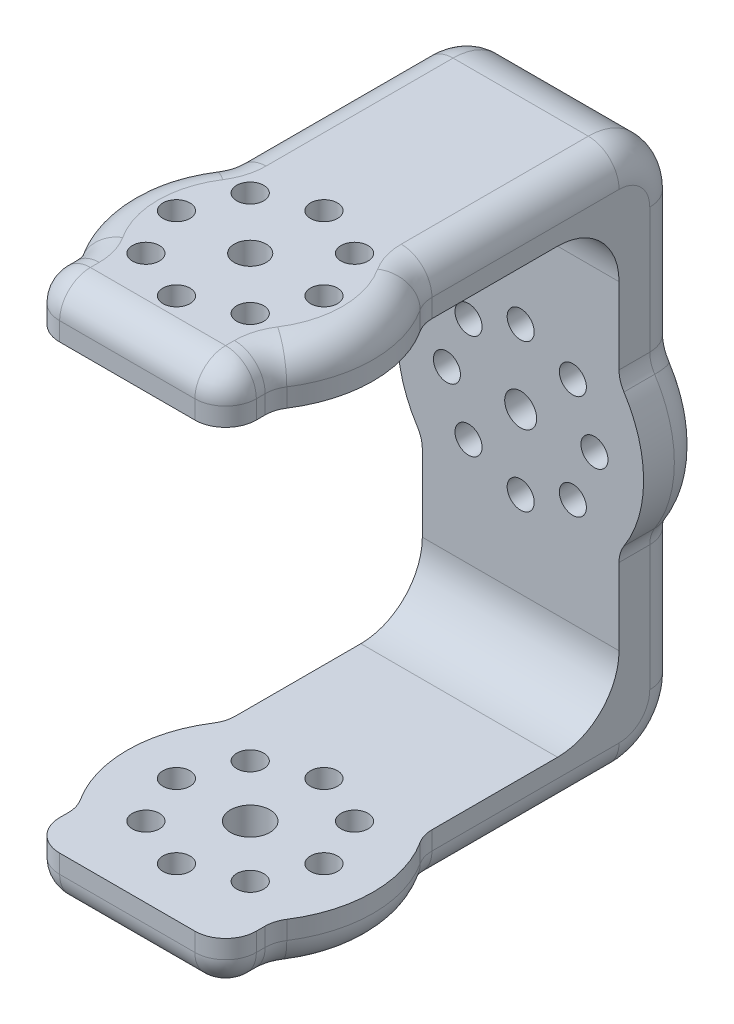
SolidWorks part; units mm, degrees
material "ABS"
ref_plane "正面" through (0, 0, 0) normal (0, 0, 1) x (1, 0, 0)
ref_plane "平面" through (0, 0, 0) normal (0, 1, 0) x (1, 0, 0)
ref_plane "右側面" through (0, 0, 0) normal (1, 0, 0) x (0, 0, -1)
sketch "ｽｹｯﾁ1" plane through (0, 0, 0) normal (0, 0, 1) x (1, 0, 0)
  line L0 (0, 0) -> (0, 36) construction
  line L1 (-8, 0) -> (8, 0)
  line L2 (-8, 0) -> (-8, 12)
  line L3 (-8, 36) -> (8, 36)
  line L4 (8, 0) -> (8, 12)
  line L5 (-8, 24) -> (-8, 36)
  line L6 (8, 24) -> (8, 36)
  circle A0 centre (0, 18) radius 6 construction
  circle A1 centre (0, 18) radius 1.3
  circle A2 centre (0, 24) radius 1.1
  circle A3 centre (4.2426, 22.2426) radius 1.1
  circle A4 centre (6, 18) radius 1.1
  circle A5 centre (4.2426, 13.7574) radius 1.1
  circle A6 centre (0, 12) radius 1.1
  circle A7 centre (-4.2426, 13.7574) radius 1.1
  circle A8 centre (-6, 18) radius 1.1
  circle A9 centre (-4.2426, 22.2426) radius 1.1
  arc A10 (-8, 24) -> (-8, 12) centre (0, 18) ccw
  arc A11 (8, 12) -> (8, 24) centre (0, 18) ccw
  point P29 (0, 18)
  dimension "D3" = 2.6
  dimension "D4" = 12
  dimension "D5" = 2.2
  dimension "D7" = 20
  dimension "D1" = 16
  dimension "D2" = 36
  dimension "D6" = 8
extrude "ﾎﾞｽ - 押し出し1" add sketch "ｽｹｯﾁ1" along normal blind 5
sketch "ｽｹｯﾁ2" plane through (0, 0, 0) normal (0, -1, 0) x (1, 0, 0)
  line L0 (8, 5) -> (8, 0) construction
  line L1 (-8, 0) -> (8, 0)
  line L2 (-8, 0) -> (-8, 21)
  line L3 (-8, 37) -> (8, 37)
  line L4 (8, 0) -> (8, 21)
  line L5 (0, 37) -> (0, 0) construction
  line L6 (-8, 33) -> (-8, 37)
  line L7 (8, 33) -> (8, 37)
  circle A0 centre (0, 27) radius 1.6
  circle A1 centre (0, 27) radius 6 construction
  circle A2 centre (6, 27) radius 1.1
  circle A3 centre (4.2426, 22.7574) radius 1.1
  circle A4 centre (0, 21) radius 1.1
  circle A5 centre (-4.2426, 22.7574) radius 1.1
  circle A6 centre (-6, 27) radius 1.1
  circle A7 centre (-4.2426, 31.2426) radius 1.1
  circle A8 centre (0, 33) radius 1.1
  circle A9 centre (4.2426, 31.2426) radius 1.1
  arc A10 (-8, 33) -> (-8, 21) centre (0, 27) ccw
  arc A11 (8, 21) -> (8, 33) centre (0, 27) ccw
  point P32 (0, 27)
  dimension "D2" = 12
  dimension "D3" = 3.2
  dimension "D5" = 2.2
  dimension "D7" = 10
  dimension "D1" = 37
  dimension "D4" = 10
  dimension "D6" = 8
extrude "ﾎﾞｽ - 押し出し2" add sketch "ｽｹｯﾁ2" along normal blind 4
sketch "ｽｹｯﾁ3" plane through (0, 36, 0) normal (0, 1, 0) x (1, 0, 0)
  line L0 (8, -5) -> (8, 0)
  line L1 (8, 0) -> (-8, 0)
  line L2 (-8, 0) -> (-8, -5)
  line L6 (8, -5) -> (-8, -5)
  line L7 (-8, -5) -> (-8, -21)
  line L8 (-8, -33) -> (-8, -37)
  line L9 (-8, -37) -> (8, -37)
  line L10 (8, -37) -> (8, -33)
  line L11 (8, -21) -> (8, -5)
  line L13 (-8, -5) -> (-8, -21)
  line L14 (-8, -33) -> (-8, -37)
  line L15 (-8, -37) -> (8, -37)
  line L16 (8, -37) -> (8, -33)
  line L17 (8, -21) -> (8, -5)
  circle A0 centre (4.2426, -22.7574) radius 1.1 construction
  circle A1 centre (0, -21) radius 1.1 construction
  arc A2 (-8, -21) -> (-8, -33) centre (0, -27) ccw
  arc A3 (8, -33) -> (8, -21) centre (0, -27) ccw
  arc A4 (-8, -21) -> (-8, -33) centre (0, -27) ccw
  arc A5 (8, -33) -> (8, -21) centre (0, -27) ccw
  circle A6 centre (-4.2426, -22.7574) radius 1.1 construction
  circle A7 centre (-6, -27) radius 1.1 construction
  circle A8 centre (-4.2426, -31.2426) radius 1.1 construction
  circle A9 centre (0, -33) radius 1.1 construction
  circle A10 centre (4.2426, -31.2426) radius 1.1 construction
  circle A11 centre (6, -27) radius 1.1 construction
  circle A12 centre (4.2426, -22.7574) radius 1.1
  circle A13 centre (0, -21) radius 1.1
  circle A14 centre (-4.2426, -22.7574) radius 1.1
  circle A15 centre (-6, -27) radius 1.1
  circle A16 centre (-4.2426, -31.2426) radius 1.1
  circle A17 centre (0, -33) radius 1.1
  circle A18 centre (4.2426, -31.2426) radius 1.1
  circle A19 centre (6, -27) radius 1.1
  circle A20 centre (0, -27) radius 1.3
  dimension "D2" = 2.6
  dimension "D1" = 0
extrude "ﾎﾞｽ - 押し出し3" add sketch "ｽｹｯﾁ3" along normal blind 4
fillet "ﾌｨﾚｯﾄ1" radius 5 4 edges at (0, 40, 0) (0, -4, 0) (0, 0, 5) (0, 36, 5)
fillet "ﾌｨﾚｯﾄ2" radius 2.5 16 edges at (8, 12, 2.5) (8, 24, 2.5) (8, 38, 21) (8, 38, 33) (8, 38, 37) (-8, 38, 37) (-8, 38, 33) (-8, 38, 21) (-8, 24, 2.5) (-8, 12, 2.5) (-8, -2, 21) (-8, -2, 33) (-8, -2, 37) (8, -2, 37) (8, -2, 21) (8, -2, 33)
fillet "ﾌｨﾚｯﾄ3" radius 2.5 40 edges at (8, -2.5355, 1.4645) (8, -4, 12.6088) (8.1021, -4, 20.9248) (10, -4, 27) (8.1021, -4, 33.0752) (8, -4, 34.1412) (7.2678, -4, 36.2678) (0, -4, 37) (-7.2678, -4, 36.2678) (-8, -4, 34.1412) (-8.1021, -4, 33.0752) (-10, -4, 27) (-8.1021, -4, 20.9248) (-8, -4, 12.6088) (-8, -2.5355, 1.4645) (-8, 6.1088, 0) (-8.1021, 11.9248, 0) (-10, 18, 0) (-8.1021, 24.0752, 0) (-8, 29.8912, 0) (-8, 38.5355, 1.4645) (-8, 40, 12.6088) (-8.1021, 40, 20.9248) (-10, 40, 27) (-8.1021, 40, 33.0752) (-8, 40, 34.1412) (-7.2678, 40, 36.2678) (0, 40, 37) (7.2678, 40, 36.2678) (8, 40, 34.1412) (8.1021, 40, 33.0752) (10, 40, 27) (8.1021, 40, 20.9248) (8, 40, 12.6088) (8, 38.5355, 1.4645) (8, 29.8912, 0) (8.1021, 24.0752, 0) (10, 18, 0) (8.1021, 11.9248, 0) (8, 6.1088, 0)
